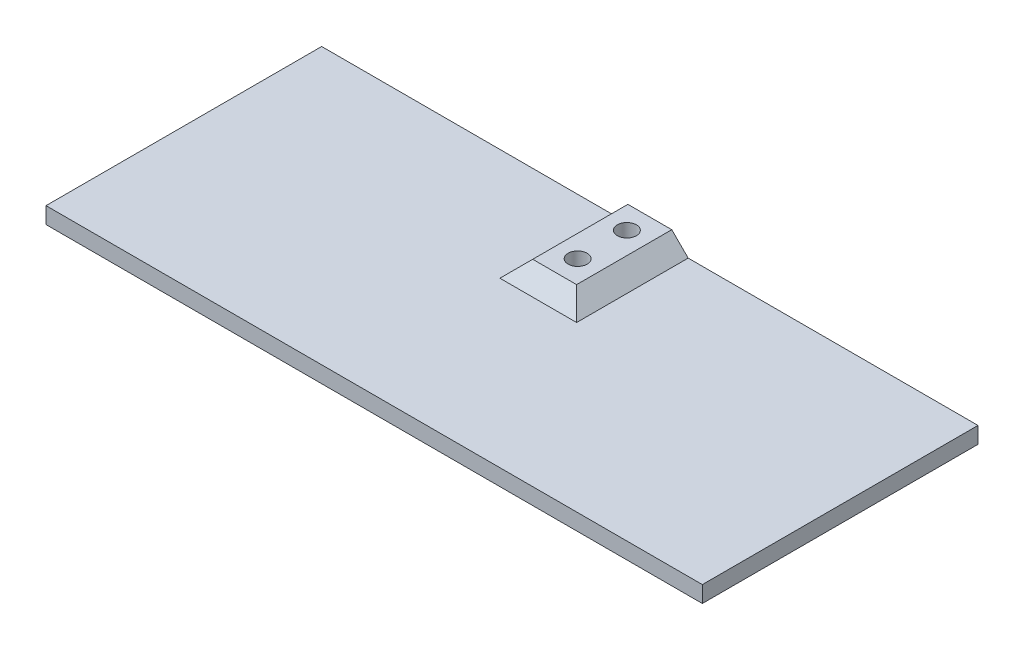
SolidWorks part; units mm, degrees
ref_plane "Front Plane" through (0, 0, 0) normal (0, 0, 1) x (1, 0, 0)
ref_plane "Top Plane" through (0, 0, 0) normal (0, 1, 0) x (1, 0, 0)
ref_plane "Right Plane" through (0, 0, 0) normal (1, 0, 0) x (0, 0, -1)
sketch "Sketch2" plane through (0, 0, 0) normal (0, 1, 0) x (1, 0, 0)
  line L1 (-100, -42) -> (100, -42)
  line L2 (-100, -42) -> (-100, 42)
  line L3 (-100, 42) -> (100, 42)
  line L4 (100, -42) -> (100, 42)
  line L5 (-100, -42) -> (100, 42) construction
  line L6 (-100, 42) -> (100, -42) construction
  point P0 (0, 0)
  dimension "D1" = 84
  dimension "D2" = 200
extrude "Boss-Extrude1" add sketch "Sketch2" along normal blind 5
sketch "Sketch5" plane through (0, 5, 0) normal (0, 1, 0) x (1, 0, 0)
  line L0 (100, 42) -> (-100, 42) construction
  line L1 (-100, 42) -> (-60.0313, 42) construction
  line L10 (-6.6876, 42) -> (6.6876, 42)
  line L11 (-6.6876, 42) -> (-6.6876, 13)
  line L12 (-6.6876, 13) -> (6.6876, 13)
  line L13 (6.6876, 42) -> (6.6876, 13)
  line L14 (-46.6562, 42) -> (-6.6876, 42) construction
  line L15 (6.6876, 42) -> (46.6562, 42) construction
  line L16 (60.0313, 42) -> (100, 42) construction
  point P3 (60.0313, 42)
  point P4 (0, 0)
  point P6 (0, 13)
  dimension "D1" = 13.3751
  dimension "D2" = 29
extrude "Boss-Extrude2" add sketch "Sketch5" along normal blind 5
hole_wizard "CBORE for M5 SHCS4" positions "Sketch3" profile "Sketch4" counterbore size "M5" standard "ANSI Metric" end condition through all
sketch "Sketch3" plane through (0, 0, 0) normal (0, -1, 0) x (-1, 0, 0)
  line L1 (-53.175, -20) -> (-53.175, -35) construction
  line L2 (-53.175, 20) -> (-53.175, -20) construction
  circle A0 centre (-53.175, -20) radius 2.5 construction
  circle A1 centre (-53.175, -35) radius 2.5 construction
  point P31 (-53.175, 0)
  point P32 (0, 35)
  point P34 (0, 20)
  point P48 (0, 0)
  point P49 (0, 0)
  dimension "D2" = 5
  dimension "D1" = 15
  dimension "D3" = 15
  dimension "D4" = 40
  dimension "D5" = 53.175
sketch "Sketch4" plane through (0, 0, -20) normal (1, 0, 0) x (0, 0, -1)
  line L0 (0, 0) -> (0, 10)
  line L1 (0, 10) -> (2.9, 10)
  line L3 (2.9, 10) -> (2.9, 5)
  line L4 (5, 5) -> (2.9, 5)
  line L5 (5, 5) -> (5, 0.021)
  line L6 (5, 0.021) -> (5.025, 0)
  line L7 (5.025, 0) -> (0, 0)
  line L8 (-5, 0.021) -> (-5.025, 0) construction
  line L11 (0, -6.35) -> (0, 107.95) construction
  dimension "Thru Hole Dia." = 5.8
  dimension "Thru Hole Depth" = 10
  dimension "C'Bore Dia." = 10
  dimension "C'Bore Depth" = 5
  dimension "Near C'Sink Dia." = 10.05
  dimension "Near C'Sink Angle" = 100
chamfer "Chamfer1" distance 5 angle 45 3 edges at (-6.6876, 5, -27.5) (0, 5, -13) (6.6876, 5, -27.5)
